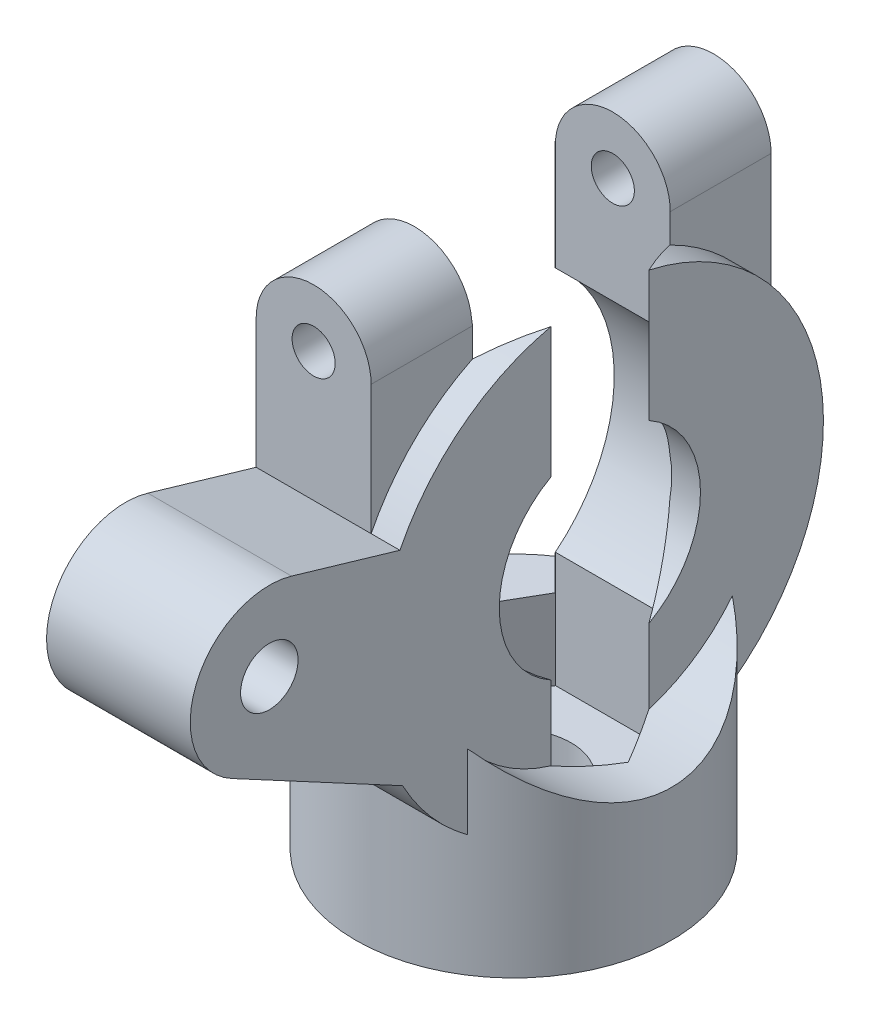
SolidWorks part; units mm, degrees
note: The reader was unsure of these and kept them because the rebuilt part matched: shared geometry of "Sketch3<2>", "Sketch2<2>".
ref_plane "Front Plane" through (0, 0, 0) normal (0, 0, 1) x (1, 0, 0)
ref_plane "Top Plane" through (0, 0, 0) normal (0, 1, 0) x (1, 0, 0)
ref_plane "Right Plane" through (0, 0, 0) normal (1, 0, 0) x (0, 0, -1)
sketch "Sketch1" plane through (0, 0, 0) normal (0, 1, 0) x (1, 0, 0)
  circle A0 centre (0, 0) radius 11
  circle A1 centre (0, 0) radius 4
  dimension "D1" = 22
  dimension "D2" = 8
extrude "Boss-Extrude1" add sketch "Sketch1" along normal blind 10
sketch "Sketch3" plane through (0, 0, 0) normal (1, 0, 0) x (0, 0, -1)
  line L0 (11, 10) -> (-11, 10) construction
  circle A0 centre (0, 21) radius 11
  circle A1 centre (0, 21) radius 15.5563
  dimension "D1" = 22
extrude "Boss-Extrude2" add sketch "Sketch3" along normal mid plane 8
sketch "Sketch2" plane through (0, 10, 0) normal (0, 1, 0) x (1, 0, 0)
  line L0 (-21.6435, 0) -> (19.7802, 0) construction
  line L1 (3.9837, 6.9) -> (-3.9837, 6.9)
  line L2 (-3.9837, 6.9) -> (-7.9674, 0)
  line L3 (-7.9674, 0) -> (-3.9837, -6.9)
  line L4 (-3.9837, -6.9) -> (3.9837, -6.9)
  line L5 (3.9837, -6.9) -> (7.9674, 0)
  line L6 (7.9674, 0) -> (3.9837, 6.9)
  circle A0 centre (0, 0) radius 6.9 construction
  dimension "D1" = 13.8
extrude "Cut-Extrude1" cut sketch "Sketch2" against normal blind 5.6 and the other way through all
sketch "Sketch9" plane through (0, 10, 0) normal (0, 1, 0) x (1, 0, 0)
  line L0 (4, 6.8718) -> (4, 10.247)
  line L1 (4, -6.8718) -> (7.9674, 0)
  line L2 (7.9674, 0) -> (4, 6.8718)
  line L3 (4, -10.247) -> (4, -6.8718)
  arc A0 (4, 10.247) -> (4, -10.247) centre (0, 0) cw
  arc A1 (4, -10.247) -> (4, 10.247) centre (0, 0) ccw construction
  line M1 (4, 10.247) -> (4, 6.8718)
  line M2 (4, 6.8718) -> (7.9674, 0)
  line M3 (7.9674, 0) -> (4, -6.8718)
  line M4 (4, -6.8718) -> (4, -10.247)
  arc M5 (4, -10.247) -> (4, 10.247) centre (0, 0) ccw
extrude "Boss-Extrude4" add sketch "Sketch9" along normal blind 10 contours M5 M1 M2 M3 M4
sketch "Sketch4" plane through (4, 0, 0) normal (1, 0, 0) x (0, 0, -1)
  line L0 (-6.8718, 34.9563) -> (-6.8718, 40.9563)
  line L1 (-6.8718, 40.9563) -> (-13.9144, 40.9563)
  line L2 (-13.9144, 40.9563) -> (-13.9144, 27.9563)
  line L3 (-6.8718, 37.9563) -> (18.7793, 37.9563) construction
  line L4 (-13.9144, 40.9563) -> (18.7793, 40.9563) construction
  line L5 (0, 8.8743) -> (0, 51.341) construction
  line L6 (6.8718, 34.9563) -> (6.8718, 40.9563)
  line L7 (6.8718, 40.9563) -> (13.9144, 40.9563)
  line L8 (13.9144, 40.9563) -> (13.9144, 27.9563)
  arc A0 (-6.8718, 34.9563) -> (-10.247, 9.2953) centre (0, 21) ccw construction
  arc A1 (-13.9144, 27.9563) -> (-6.8718, 34.9563) centre (0, 21) cw
  arc A2 (13.9144, 27.9563) -> (6.8718, 34.9563) centre (0, 21) ccw
  dimension "D1" = 3
  dimension "D2" = 13
extrude "Boss-Extrude3" add sketch "Sketch4" against normal up to surface (8 mm away) up to face at (-4, 17.8591, -9.8289)
extrude "Boss-Extrude5" add sketch "Sketch3<2>" along normal blind 2 from surface at 4 contours A0 | A1 A0 starting at face at (4, 28.6626, -10.5982)
sketch "Sketch3<2>" plane through (0, 0, 0) normal (1, 0, 0) x (0, 0, -1) same geometry as "Sketch3"
extrude "Cut-Extrude2" cut sketch "Sketch2<2>" along normal through all and the other way up to surface (5.6 mm away) other way up to face at (0, 4.4, 4)
sketch "Sketch2<2>" plane through (0, 10, 0) normal (0, 1, 0) x (1, 0, 0) same geometry as "Sketch2"
sketch "Sketch13" plane through (6, 0, 0) normal (1, 0, 0) x (0, 0, -1)
  circle A0 centre (0, 21) radius 7
  dimension "D1" = 14
extrude "Cut-Extrude3" cut sketch "Sketch13" against normal through all both and the other way through all
sketch "Sketch14" plane through (0, 0, 13.9144) normal (0, 0, 1) x (1, 0, 0)
  line L0 (-4, 27.9563) -> (-4, 40.9563) construction
  line L2 (4, 40.9563) -> (4, 27.9563) construction
  line L3 (-4, 40.9563) -> (4, 40.9563) construction
  line L4 (-4, 36.9563) -> (-4, 43.4737)
  line L5 (-4, 43.4737) -> (4, 43.4737)
  line L6 (4, 43.4737) -> (4, 36.9563)
  circle A0 centre (0, 36.9563) radius 1.5
  arc A1 (-4, 36.9563) -> (4, 36.9563) centre (0, 36.9563) cw
  dimension "D1" = 3
  dimension "D2" = 6.5173
extrude "Cut-Extrude5" cut sketch "Sketch14" against normal through all both and the other way through all
sketch "Sketch15" plane through (6, 0, 0) normal (1, 0, 0) x (0, 0, -1)
  circle A0 centre (0, 21) radius 11.7899
extrude "Cut-Extrude6" cut sketch "Sketch15" along normal blind 8 from surface at 0 starting at face at (6, 22.8359, -8.44)
sketch "Sketch16" plane through (-4, 0, 0) normal (-1, 0, 0) x (0, 0, 1)
  line L0 (0, -22.8948) -> (0, 64.8948) construction
  line L1 (23, -23.5851) -> (23, 63.1608) construction
  line L2 (0, 21) -> (82.2467, 34.911) construction
  line L3 (11, 21) -> (-11, 21) construction
  line L4 (25.5993, 20.0432) -> (6.8718, 10)
  line L5 (13.9144, 27.9563) -> (21.4516, 30.1677)
  circle A0 centre (23, 24.8902) radius 2
  arc A1 (6.8718, 12.4106) -> (6.8718, 29.5894) centre (0, 21) ccw construction
  arc A2 (-6.8718, 29.5894) -> (-6.8718, 12.4106) centre (0, 21) ccw construction
  arc A3 (25.5993, 20.0432) -> (21.4516, 30.1677) centre (23, 24.8902) ccw
  arc M14 (10.247, 9.2953) -> (13.9144, 27.9563) centre (0, 21) ccw
  dimension "D2" = 4
  dimension "D3" = 5.5
  dimension "D1" = 80.4
  dimension "19" = 23
extrude "Boss-Extrude6" add sketch "Sketch16" against normal up to surface (10 mm away) contours L4 A3 L5 A0 M14 up to face at (6, 18.5733, -7.4789)
